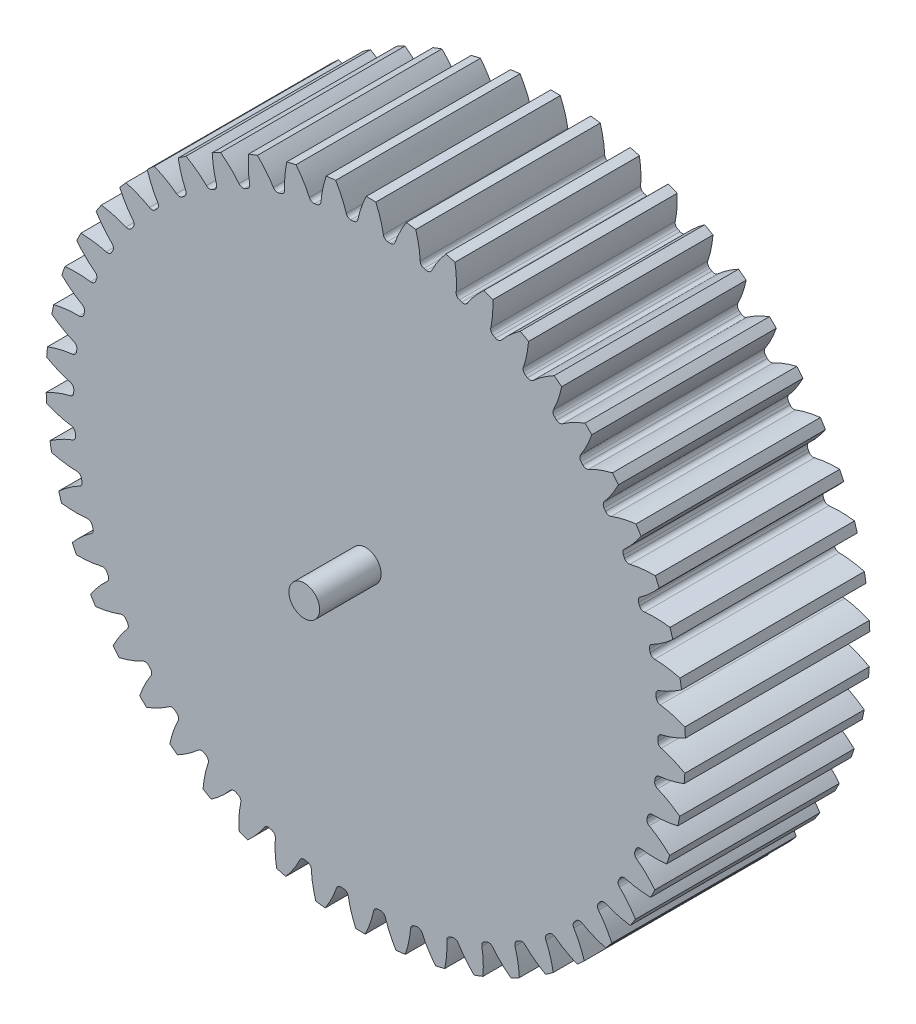
SolidWorks part; units mm, degrees
ref_plane "前视基准面" through (0, 0, 0) normal (0, 0, 1) x (1, 0, 0)
ref_plane "上视基准面" through (0, 0, 0) normal (0, 1, 0) x (1, 0, 0)
ref_plane "右视基准面" through (0, 0, 0) normal (1, 0, 0) x (0, 0, -1)
sketch "草图2" plane through (0, 0, 0) normal (0, 0, 1) x (1, 0, 0)
  spline S0 degree 4 poles (46.9846, 0) (47.0061, 0.0004) (47.0661, 0.0025) (47.1796, 0.0108) (47.3643, 0.0305) (47.5989, 0.0648) (47.901, 0.1194) (48.2551, 0.197) (48.6421, 0.2962) (49.0604, 0.4189) (49.475, 0.5545) (49.8857, 0.7017) (50.2924, 0.8595) (50.7812, 1.0629) (51.3631, 1.3253) (52.034, 1.6561) (52.7871, 2.0634) (53.5397, 2.5066) (54.2754, 2.9735) (54.9982, 3.466) (55.7019, 3.9762) (56.3971, 4.5131) (56.9817, 4.989) (57.4902, 5.4247) (57.8815, 5.7686) (58.2355, 6.0926) (58.5753, 6.4044) (59.1303, 6.942) (59.4711, 7.2816) (59.9928, 7.8193) (60.1778, 8.0208) (60.3277, 8.1804) knots 0 0 0 0 0 0.005377 0.015084 0.028532 0.04661 0.064855 0.092111 0.119476 0.146842 0.174209 0.201575 0.228941 0.256307 0.307035 0.361767 0.4165 0.471232 0.525964 0.580697 0.635429 0.690161 0.744894 0.77226 0.799626 0.826992 0.854358 0.909091 0.954545 1 1 1 1 1 construction
  spline S1 degree 4 poles (46.9846, 0) (47.0061, 0.0004) (47.0661, 0.0025) (47.1796, 0.0108) (47.3643, 0.0305) (47.5989, 0.0648) (47.901, 0.1194) (48.2551, 0.197) (48.6421, 0.2962) (49.0604, 0.4189) (49.475, 0.5545) (49.8857, 0.7017) (50.2924, 0.8595) (50.7812, 1.0629) (51.3631, 1.3253) (52.034, 1.6561) (52.7871, 2.0634) (53.5397, 2.5066) (54.2754, 2.9735) (54.9982, 3.466) (55.7019, 3.9762) (56.3971, 4.5131) (56.9817, 4.989) (57.4902, 5.4247) (57.8815, 5.7686) (58.2355, 6.0926) (58.5753, 6.4044) (58.9674, 6.7843) (59.1763, 6.9895) (59.3166, 7.1297) knots 0 0 0 0 0 0.005377 0.015084 0.028532 0.04661 0.064855 0.092111 0.119476 0.146842 0.174209 0.201575 0.228941 0.256307 0.307035 0.361767 0.4165 0.471232 0.525964 0.580697 0.635429 0.690161 0.744894 0.77226 0.799626 0.826992 0.854358 0.909091 0.909091 0.909091 0.909091 0.909091
sketch "草图3" plane through (0, 0, 0) normal (0, 0, 1) x (1, 0, 0)
  line L0 (0, 0) -> (94.4479, 0) construction
  line L1 (0, 0) -> (0, 16.635) construction
  line L2 (0, 0) -> (75.0713, 3.4798) construction
  circle A0 centre (0, 0) radius 47.5
  circle A1 centre (0, 0) radius 52
  circle A2 centre (0, 0) radius 46.9846 construction
  circle A3 centre (0, 0) radius 50 construction
  arc A4 (47.4966, -0.5704) -> (48.0918, 0.1624) centre (48.2565, -0.5796) cw
  arc A5 (47.2401, 4.9618) -> (47.9006, 4.2872) centre (47.996, 5.0412) ccw
  spline S0 degree 4 poles (34.9111, 1999.7571) (41.6645, 33.6819) (43.5847, 0.5997) (45.4856, -0.1704) (47.3643, 0.0305) (47.5989, 0.0648) (47.901, 0.1194) (48.2551, 0.197) (48.6421, 0.2962) (49.0604, 0.4189) (49.475, 0.5545) (49.8857, 0.7017) (50.2924, 0.8595) (50.7812, 1.0629) (51.3631, 1.3253) (52.034, 1.6561) (52.7871, 2.0634) (53.5397, 2.5066) (54.2754, 2.9735) (54.9982, 3.466) (55.7019, 3.9762) (56.3971, 4.5131) (56.9817, 4.989) (57.4902, 5.4247) (57.8815, 5.7686) (58.2355, 6.0926) (60.0616, 7.7684) (66.8557, 14.8407) (-9.1165, -60.5491) (1472.6972, 1422.1038) knots -0.427453 -0.427453 -0.427453 -0.427453 -0.427453 0.005377 0.015084 0.028532 0.04661 0.064855 0.092111 0.119476 0.146842 0.174209 0.201575 0.228941 0.256307 0.307035 0.361767 0.4165 0.471232 0.525964 0.580697 0.635429 0.690161 0.744894 0.77226 0.799626 0.826992 0.854358 1.507709 1.507709 1.507709 1.507709 1.507709 only from (46.9846, 0) to (59.3166, 7.1297) construction
  spline S1 degree 4 poles (48.0918, 0.1624) (48.1767, 0.1812) (48.3676, 0.2258) (48.6629, 0.3023) (49.0604, 0.4189) (49.475, 0.5545) (49.8857, 0.7017) (50.2924, 0.8595) (50.7812, 1.0629) (51.2529, 1.2756) (51.6208, 1.4534) (51.8879, 1.5886) (51.9744, 1.633) knots 0.070295 0.070295 0.070295 0.070295 0.070295 0.092111 0.119476 0.146842 0.174209 0.201575 0.228941 0.256307 0.307035 0.331424 0.331424 0.331424 0.331424 0.331424
  spline S2 degree 4 poles (47.9006, 4.2872) (47.9869, 4.2763) (48.181, 4.2495) (48.4822, 4.2008) (48.8887, 4.1214) (49.3142, 4.0248) (49.7367, 3.9161) (50.1563, 3.7967) (50.6618, 3.6393) (51.1512, 3.4712) (51.5339, 3.3281) (51.8123, 3.2183) (51.9025, 3.1821) knots 0.070295 0.070295 0.070295 0.070295 0.070295 0.092111 0.119476 0.146842 0.174209 0.201575 0.228941 0.256307 0.307035 0.331424 0.331424 0.331424 0.331424 0.331424
  point P14 (49.9464, 2.3152)
  point P17 (49.9944, 0.7452)
  dimension "D1" = 100
  dimension "D2" = 93.9693
  dimension "D3" = 104
  dimension "D4" = 95
  dimension "D6" = 0.76
  dimension "D5" = 1.5708
extrude "凸台-拉伸2" add sketch "草图3" along normal blind 30 contours A0
extrude "凸台-拉伸3" add sketch "草图3<6>" along normal up to surface (30 mm away) from surface contours S2 A5 A0 A4 S1 A1 region at (49.3392, 2.287, 0) up to face at (47.5, 0, 30) starting at face at (47.5, 0, 0)
sketch "草图3<6>" plane through (0, 0, 0) normal (0, 0, 1) x (1, 0, 0) same geometry as "草图3"
pattern_circular "阵列(圆周)1" count 50 over 360 about axis through (0, 0, 30) along (0, 0, -1) of "凸台-拉伸3"
sketch "草图5" plane through (0, 0, 30) normal (0, 0, 1) x (1, 0, 0)
  circle A0 centre (0, 0) radius 2.5
  dimension "D1" = 5
extrude "凸台-拉伸4" add sketch "草图5" along normal blind 5 contours A0
sketch "草图7" plane through (0, 0, 35) normal (0, 0, 1) x (1, 0, 0)
  circle A1 centre (0, 0) radius 2.5
  circle A2 centre (0, 0) radius 2.5
  dimension "D1" = 0
extrude "凸台-拉伸5" add sketch "草图7" along normal blind 5
sketch "草图8" plane through (0, 0, 0) normal (0, 0, -1) x (-1, 0, 0)
  line L0 (-2, 1.5) -> (2, 1.5)
  line L1 (-2, -1.5) -> (2, -1.5)
  line L3 (200000, 0) -> (-200094.4479, 0) construction
  arc A0 (2, -1.5) -> (2, 1.5) centre (0, 0) ccw
  arc A1 (-2, 1.5) -> (-2, -1.5) centre (0, 0) ccw
  dimension "D1" = 5
  dimension "D2" = 1.5
  dimension "D3" = 1.5
extrude "切除-拉伸2" cut sketch "草图8" against normal blind 6
equation "\"m\"= 2"
equation "\"z\"= 50"
equation "\"a\"= 20"
equation "\"d\"= \"m\" * \"z\""
equation "\"da\"= ( \"z\" + 2 ) * \"m\""
equation "\"df\" = ( \"z\" - 2.5 ) * \"m\""
equation "\"db\"= \"m\" * \"z\" * cos ( \"a\" )"
equation "\"rb\"= \"db\" / 2"
equation "\"s\"= 0.5 * pi * \"m\""
equation "\"r\"= 0.38 * \"m\""
equation "\"D1@草图3\"=\"d\""
equation "\"D2@草图3\"=\"db\""
equation "\"D3@草图3\"=\"da\""
equation "\"D4@草图3\"=\"df\""
equation "\"D5@草图3\"=\"s\"/2"
equation "\"D6@草图3\"=\"r\""
